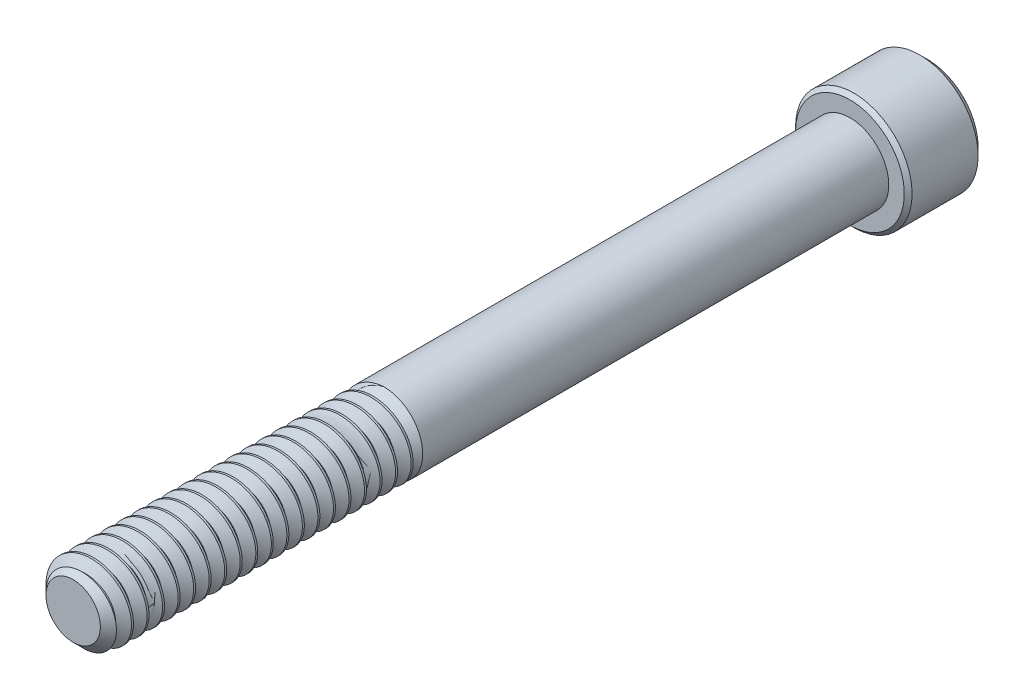
SolidWorks part; units mm, degrees
material "Cast Alloy Steel"
ref_plane "Front Plane" through (0, 0, 0) normal (0, 0, 1) x (1, 0, 0)
ref_plane "Top Plane" through (0, 0, 0) normal (0, 1, 0) x (1, 0, 0)
ref_plane "Right Plane" through (0, 0, 0) normal (1, 0, 0) x (0, 0, -1)
sketch "Sketch1" plane through (0, 0, 0) normal (0, 0, 1) x (1, 0, 0)
  line L0 (0, 3.175) -> (0, -3.175) construction
  circle A0 centre (0, 0) radius 3.175
  dimension "OD" = 6.35
extrude "Extrude1" add sketch "Sketch1" against normal blind 63.5
sketch "Sketch2" plane through (0, 0, 0) normal (0, 0, 1) x (1, 0, 0)
  circle A0 centre (0, 0) radius 3.175 construction
  circle A1 centre (0, 0) radius 3.175
curve "Helix/Spiral1" pitch 1.27 height 27.94 turns 22 parameters "pitch"=1.27
chamfer "Chamfer3" distance 0.9525 angle 45 1 edges at (3.175, 0, 0)
sketch "Sketch3" plane through (0, 0, 0) normal (1, 0, 0) x (0, 0, -1)
  line L0 (-1.1112, 3.175) -> (-0.635, 2.3501)
  line L1 (-0.635, 2.3501) -> (-0.4763, 2.3501)
  line L2 (-0.4763, 2.3501) -> (0, 3.175)
  line L3 (-1.1112, 3.175) -> (0, 3.175)
  line L4 (-0.5556, 3.175) -> (-0.5556, 2.3501) construction
  line L5 (-0.8731, 2.7626) -> (-0.2381, 2.7626) construction
  line L6 (0, 3.175) -> (0, -3.175) construction
  dimension "D1" = 0.1588
  dimension "D2" = 0.635
  dimension "D3" = 60
sweep "Cut-Sweep1" cut profiles "Sketch3" path "Helix/Spiral1"
sketch "Sketch5" plane through (0, 0, 0) normal (1, 0, 0) x (0, 0, -1)
  line L1 (63.5, 3.175) -> (25.4, 3.175)
  line L2 (63.5, 3.175) -> (63.5, 0)
  line L3 (63.5, 0) -> (25.4, 0)
  line L4 (25.4, 3.175) -> (25.4, 0) construction
  line L6 (0, 0) -> (9.9695, 0) construction
  line L8 (25.4, 3.175) -> (22.225, 0)
  line L9 (22.225, 0) -> (25.4, 0)
  line L10 (63.5, -3.175) -> (63.5, 3.175) construction
  dimension "D1" = 45
  dimension "Thread min" = 25.4
revolve "partially thread" add sketch "Sketch5" angle 360 about L6
sketch "Sketch6" plane through (0, 0, -63.5) normal (0, 0, -1) x (-1, 0, 0)
  circle A0 centre (0, 0) radius 4.7625
  dimension "head dia" = 9.525
extrude "Extrude2" add sketch "Sketch6" along normal blind 6.35
sketch "Sketch7" plane through (0, 0, -69.85) normal (0, 0, -1) x (-1, 0, 0)
  line L1 (0, 2.7496) -> (-2.3812, 1.3748)
  line L2 (-2.3812, 1.3748) -> (-2.3813, -1.3748)
  line L3 (-2.3813, -1.3748) -> (0, -2.7496)
  line L4 (0, -2.7496) -> (2.3813, -1.3748)
  line L5 (2.3813, -1.3748) -> (2.3813, 1.3748)
  line L6 (2.3813, 1.3748) -> (0, 2.7496)
  circle A0 centre (0, 0) radius 2.3813 construction
  dimension "hex dia" = 4.7625
extrude "Cut-Extrude1" cut sketch "Sketch7" against normal blind 3.5719
sketch "Sketch8" plane through (0, 0, -69.85) normal (0, 0, -1) x (-1, 0, 0)
  circle A0 centre (0, 0) radius 2.7496
extrude "Cut-Extrude2" cut sketch "Sketch8" against normal blind 0.635 draft 45
chamfer "Chamfer1" distance 0.635 angle 45 1 edges at (-4.7625, 0, -69.85)
chamfer "Chamfer2" distance 0.3175 angle 45 1 edges at (-4.7625, 0, -63.5)
sketch "Sketch9" plane through (0, 0, 0) normal (1, 0, 0) x (0, 0, -1)
  line L0 (0, 3.175) -> (0, -3.175) construction
  line L1 (6.985, 3.175) -> (6.985, -3.175) construction
  line L2 (63.5, 4.7625) -> (63.5, -4.7625) construction
  line L3 (69.85, 4.7625) -> (69.85, -4.7625) construction
  line L4 (69.85, 0) -> (0, 0) construction
  line L5 (61.6852, 3.175) -> (61.6852, -3.175) construction
  dimension "D1" = 6.985
  dimension "D2" = 6.35
  dimension "D3" = 9.525
  dimension "D4" = 63.5
  dimension "Thread Length" = 61.6852
equation "\"D3@Helix/Spiral1\" = \"Thread min@Sketch5\"+(\"pitch@Helix/Spiral1\"*2)"
equation "\"D1@Sketch3\" = \"pitch@Helix/Spiral1\"*.125"
equation "\"D2@Sketch3\" = \"pitch@Helix/Spiral1\"*.5"
equation "\"D1@Cut-Extrude1\" = \"hex dia@Sketch7\"*.75"
equation "\"D1@Chamfer1\" = \"head depth@Extrude2\"/10"
equation "\"D1@Sketch9\" = \"pitch@Helix/Spiral1\"*5.5"
equation "\"D1@Chamfer2\" = \"D1@Chamfer1\"/2"
equation "\"D1@Cut-Extrude2\" = \"D1@Chamfer2\"*2"
equation "\"D1@Chamfer3\" = \"pitch@Helix/Spiral1\"*.750"
equation "\"D2@Sketch9\" = \"head depth@Extrude2\""
equation "\"D3@Sketch9\" = \"head dia@Sketch6\""
equation "\"D4@Sketch9\" = \"screw length@Extrude1\""
